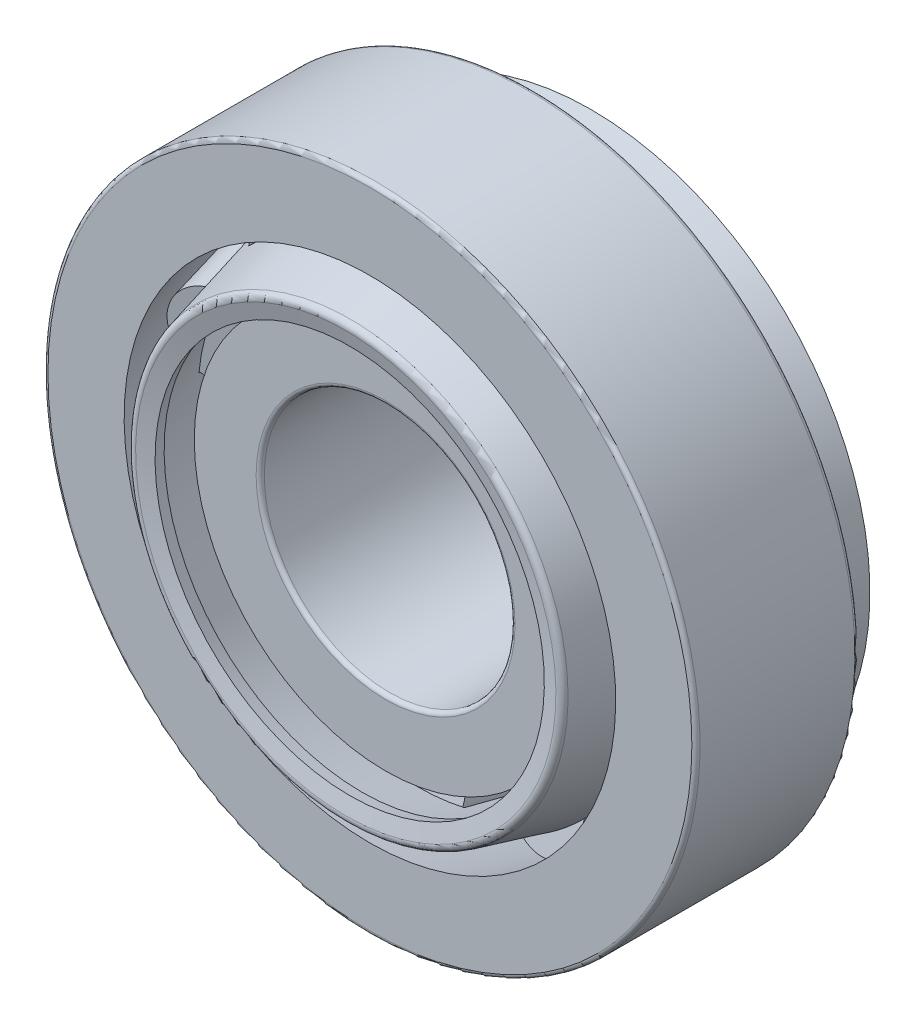
SolidWorks part; units mm, degrees
ref_plane "Front Plane" through (0, 0, 0) normal (0, 0, 1) x (1, 0, 0)
ref_plane "Top Plane" through (0, 0, 0) normal (0, 1, 0) x (1, 0, 0)
ref_plane "Right Plane" through (0, 0, 0) normal (1, 0, 0) x (0, 0, -1)
sketch "Sketch1" plane through (0, 0, 0) normal (1, 0, 0) x (0, 0, -1)
  line L0 (-5.25, 0) -> (9.75, 0) construction
  line L1 (0, 0) -> (0, 26) construction
  line L2 (-5.25, 10) -> (9.75, 10) construction
  line L3 (9.75, 10) -> (9.75, 16.4) construction
  line L4 (9.75, 16.4) -> (-5.25, 12.5821) construction
  line L5 (-5.25, 12.5821) -> (-5.25, 10) construction
  line L7 (-6.5, 26) -> (6.5, 26)
  line L8 (6.5, 26) -> (6.5, 22.9088)
  line L9 (6.5, 22.9088) -> (-6.5, 19.6)
  line L10 (-6.5, 19.6) -> (-6.5, 26)
  line L12 (10.6848, 23.974) -> (11.5616, 20.5291) construction
  line L13 (-7.2348, 12.0769) -> (-8.1116, 15.5218) construction
  line L14 (-5.25, 12.5821) -> (-7.2348, 12.0769) construction
  line L15 (-5.25, 12.5821) -> (12.4384, 17.0843) construction
  line L20 (-5.25, -12.5821) -> (12.4384, -17.0843) construction
  line L21 (-5.25, -12.5821) -> (-7.2348, -12.0769) construction
  line L22 (-7.2348, -12.0769) -> (-8.9884, -18.9666) construction
  line L23 (10.6848, -23.974) -> (12.4384, -17.0843) construction
  line L24 (-5.25, -12.5821) -> (-5.25, -10) construction
  line L25 (9.75, -16.4) -> (-5.25, -12.5821) construction
  line L26 (9.75, -10) -> (9.75, -16.4) construction
  line L27 (-5.25, -10) -> (9.75, -10) construction
  line L28 (-6.5, -19.6) -> (-6.5, -26) construction
  line L29 (6.5, -22.9088) -> (-6.5, -19.6) construction
  line L30 (6.5, -26) -> (6.5, -22.9088) construction
  line L31 (-6.5, -26) -> (6.5, -26) construction
  line L32 (11.1232, 22.2515) -> (-8.55, 17.2442) construction
  line L33 (12, 18.8067) -> (-7.6732, 13.7994) construction
  line L34 (11.5616, 20.5291) -> (12.4384, 17.0843) construction
  line L35 (-8.1116, 15.5218) -> (-8.9884, 18.9666) construction
  point P5 (0, 10)
  point P37 (0, -10)
  dimension "OD" = 52
  dimension "Shaft Dia" = 20
  dimension "D3" = 6.4
  dimension "Width" = 13
  dimension "Inner Ring Width" = 15
  dimension "Cage Width" = 16.25
  dimension "Ab" = 3.3
  dimension "Retainer Width" = 20.55
  dimension "D1" = 14.28
revolve "Revolve1" add sketch "Sketch1" angle 360 about L0
sketch "Sketch3" plane through (0, 0, 0) normal (1, 0, 0) x (0, 0, -1)
  line L1 (-5.25, 16.2501) -> (-6.3296, 20.4919) construction
  line L4 (-7.2348, 12.0769) -> (-8.1116, 15.5218) construction
  line L5 (-5.25, 12.5821) -> (-5.25, 10) construction
  line L6 (6.5, 26) -> (6.5, 22.9088) construction
  line L7 (6.5, 19.2408) -> (-5.25, 16.2501) construction
  line L13 (-8.1116, 15.5218) -> (-5.25, 16.2501) construction
  point P1 (-2.3884, 16.9785)
sketch "Sketch5" plane through (0, 0, 0) normal (1, 0, 0) x (0, 0, -1)
  line L0 (9.75, 16.4) -> (-5.25, 12.5821) construction
  line L1 (7.3768, 15.796) -> (-1.5116, 13.5336)
  line L2 (-5.25, 15.2561) -> (-5.25, 10)
  line L3 (-5.25, 10) -> (9.75, 10)
  line L4 (9.75, 10) -> (9.75, 17.5184)
  line L5 (-5.25, 15.2561) -> (-1.95, 15.2561)
  line L7 (-1.95, 15.2561) -> (-1.5116, 13.5336)
  line L8 (12, 18.8067) -> (-7.6732, 13.7994) construction
  line L9 (6.9384, 17.5184) -> (7.3768, 15.796)
  line L10 (6.9384, 17.5184) -> (9.75, 17.5184)
  line L11 (6.5, 19.2408) -> (7.3768, 15.796) construction
  line L12 (-2.3884, 16.9785) -> (-1.5116, 13.5336) construction
revolve "Revolve4" add sketch "Sketch5" angle 360 about L0
sketch "Sketch2" plane through (0, 0, 0) normal (1, 0, 0) x (0, 0, -1)
  line L1 (-8.4267, 16.7597) -> (-8.1116, 15.5218)
  line L3 (-8.1116, 15.5218) -> (-7.1425, 15.7685)
  line L5 (11.3699, 21.2824) -> (11.1232, 22.2515)
  line L6 (-8.1116, 15.5218) -> (-5.25, 16.2501) construction
  line L7 (-7.1425, 15.7685) -> (-7.3342, 16.5218)
  line L9 (11.1232, 22.2515) -> (-8.0654, 17.3675)
  line L10 (-7.3342, 16.5218) -> (11.3699, 21.2824)
  line L16 (0, 0) -> (-5.25, 0) construction
  line L17 (-5.25, 12.5821) -> (-5.25, -12.5821) construction
  arc A0 (-8.4267, 16.7597) -> (-8.0654, 17.3675) centre (-7.9421, 16.883) cw
  point P12 (-8.55, 17.2442)
  dimension "D2" = 0.5
  dimension "D1" = 1
revolve "Revolve2" add sketch "Sketch2" angle 360 about L0
ref_plane "Plane1" through (0, 16.9785, 2.3884) normal (0, -0.2467, 0.9691) x (1, 0, 0)
sketch "Sketch8" plane through (0, 16.9785, 2.3884) normal (0, -0.2467, 0.9691) x (1, 0, 0)
  circle A0 centre (0, 0) radius 3.5547
extrude "Cut-Extrude1" cut sketch "Sketch8" against normal up to vertex (9.1718 mm away) up to point (0, 19.2408, -6.5)
sketch "Sketch10" plane through (0, 16.9785, 2.3884) normal (0, -0.2467, 0.9691) x (1, 0, 0)
  line L0 (0, 0) -> (0, 3.4277) construction
  circle A0 centre (0, 0) radius 3.4277
  dimension "D1" = 0.127
extrude "Boss-Extrude1" add sketch "Sketch10" against normal up to vertex (9.1718 mm away) separate body up to point (0, 19.2408, -6.5)
sketch "Sketch7" plane through (0, 0, 0) normal (0, 0, 1) x (1, 0, 0)
  line L0 (0, 0) -> (-3.477, 16.89) construction
  line L1 (0, 0) -> (3.477, 16.89) construction
  circle A1 centre (0, 0) radius 17.2442 construction
  ellipse E1 centre (0, 16.9785) end of major axis (-3.4277, 16.9785) minor radius 3.3218 construction
  dimension "D1" = 23.265
ref_axis "Axis1" through (0, 0, -9.75) along (0, 0, 1)
pattern_circular "CirPattern1" count 10 over 360 about axis through (0, 0, -9.75) along (0, 0, 1) of "Cut-Extrude1"
pattern_circular "CirPattern2" count 10 over 360 about axis through (0, 0, -9.75) along (0, 0, 1) of bodies 851 403
fillet "Fillet1" radius 0.325 2 edges at (0, -26, -6.5) (0, -26, 6.5)
fillet "Fillet2" radius 0.325 2 edges at (0, -10, -9.75) (0, -10, 5.25)
sketch "Sketch12" plane through (0, 0, 0) normal (1, 0, 0) x (0, 0, -1)
  line L0 (9.75, 10) -> (9.75, 16.4) construction
  line L1 (-5.25, 10) -> (9.75, 10) construction
  line L2 (-5.25, 12.5821) -> (-5.25, 10) construction
  line L3 (9.75, 16.4) -> (-5.25, 12.5821) construction
  line L4 (9.75, 10) -> (9.75, 16.4)
  line L5 (-5.25, 10) -> (9.75, 10)
  line L6 (-5.25, 12.5821) -> (-5.25, 10)
  line L7 (9.75, 16.4) -> (-5.25, 12.5821)
  line L8 (-5.25, -12.5821) -> (-5.25, -10) construction
  line L9 (-5.25, -10) -> (9.75, -10) construction
  line L10 (9.75, -10) -> (9.75, -16.4) construction
  line L11 (9.75, -16.4) -> (-5.25, -12.5821) construction
  line L12 (-5.25, -12.5821) -> (-5.25, -10)
  line L13 (-5.25, -10) -> (9.75, -10)
  line L14 (9.75, -10) -> (9.75, -16.4)
  line L15 (9.75, -16.4) -> (-5.25, -12.5821)
  line L25 (-5.25, 0) -> (9.75, 0) construction
  line L26 (-5.25, 0) -> (9.75, 0) construction
  line L29 (-5.25, 10) -> (-5.25, -10)
  line L36 (9.75, 10) -> (9.75, -10)
equation "\"D3@Sketch1\"=(\"OD@Sketch1\"-\"Shaft Dia@Sketch1\") /5"
equation "\"D1@Fillet1\"= \"Width@Sketch1\" * .025"
equation "\"D1@Fillet2\" = \"D1@Fillet1\""
equation "\"Rollers@CirPattern2\"=(360/\"D1@Sketch7\")/1.50"
equation "\"D1@CirPattern1\"=\"Rollers@CirPattern2\""
